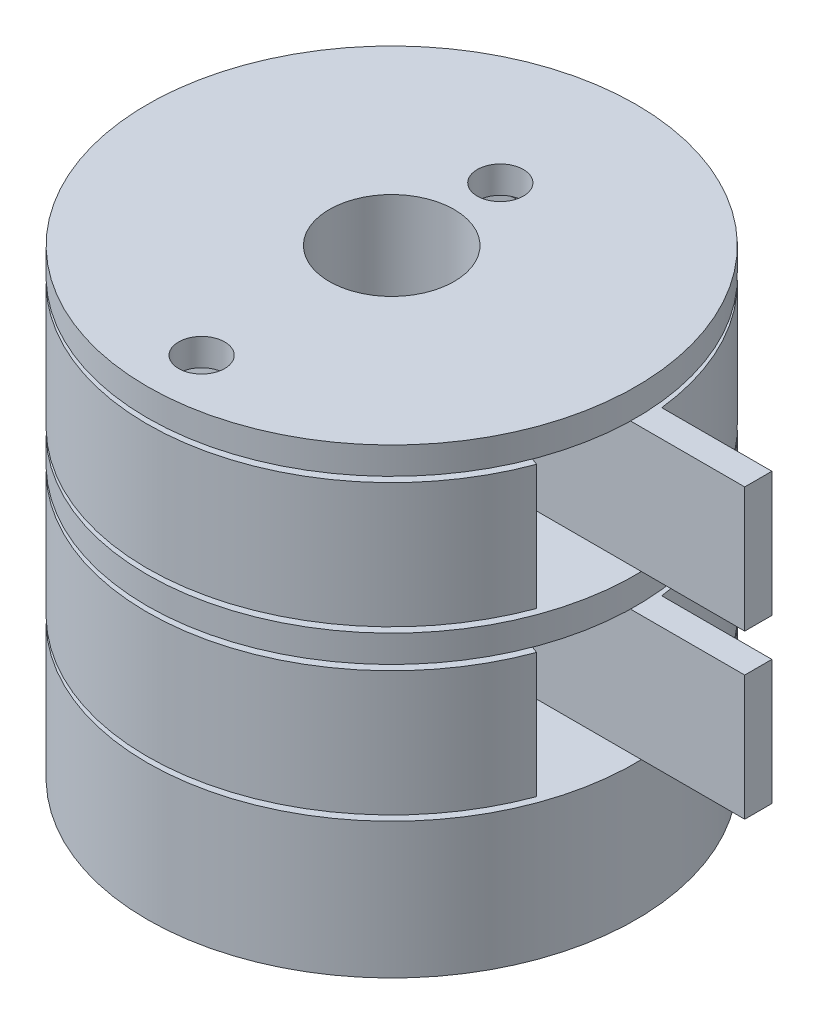
SolidWorks part; units mm, degrees
ref_plane "Plano frontal" through (0, 0, 0) normal (0, 0, 1) x (1, 0, 0)
ref_plane "Plano superior" through (0, 0, 0) normal (0, 1, 0) x (1, 0, 0)
ref_plane "Plano direito" through (0, 0, 0) normal (1, 0, 0) x (0, 0, -1)
sketch "Esboço1" plane through (0, 0, 0) normal (0, 0, 1) x (1, 0, 0)
  line L0 (9, 3.5) -> (3.7, 3.5)
  line L1 (2.3, 9.5) -> (2.3, -7.5)
  line L2 (2.3, -7.5) -> (9, -7.5)
  line L3 (9, -7.5) -> (9, -2.5)
  line L4 (9, -2.5) -> (3.7, -2.5)
  line L5 (3.7, -2.5) -> (3.7, 2.5)
  line L6 (3.7, 2.5) -> (9, 2.5)
  line L7 (9, 2.5) -> (9, 3.5)
  line L8 (0, 0) -> (9.3553, 0) construction
  line L9 (0, 0) -> (0, 2.2181) construction
  line L10 (3.7, 3.5) -> (3.7, 8.5)
  line L11 (3.7, 8.5) -> (9, 8.5)
  line L12 (9, 8.5) -> (9, 9.5)
  line L13 (9, 9.5) -> (2.3, 9.5)
  point P12 (3.7, 0)
  point P15 (1.8, 7.7314)
  dimension "D1" = 4.6
  dimension "D2" = 18
  dimension "D3" = 1.4
  dimension "D4" = 1
  dimension "D5" = 5
  dimension "D6" = 5
revolve "Revolução1" add sketch "Esboço1" angle 360 about L9
sketch "Esboço2" plane through (0, 3.5, 0) normal (0, 1, 0) x (1, 0, 0)
  line L0 (-2.245, 0.5) -> (2.245, 0.5)
  circle A0 centre (0, 0) radius 2.3 construction
  arc A1 (2.245, 0.5) -> (-2.245, 0.5) centre (0, 0) ccw
  arc A2 (-2.245, 0.5) -> (2.245, 0.5) centre (0, 0) ccw construction
  dimension "D1" = 2.8
extrude "Ressalto-extrusão2" [suppressed] add sketch "Esboço2" against normal through all
sketch "Esboço3" plane through (0, 2.5, 0) normal (0, -1, 0) x (1, 0, 0)
  circle A0 centre (0, -4) radius 0.85
  circle A1 centre (0, 7) radius 0.85
  point P4 (0, 0)
  dimension "D3" = 1.7
  dimension "D1" = 7
  dimension "D2" = 4
extrude "Corte-extrusão1" cut sketch "Esboço3" against normal through all both and the other way through all
sketch "Esboço4" plane through (0, 0, 0) normal (1, 0, 0) x (0, 0, -1)
  line L0 (-9, -7.5) -> (9, -7.5) construction
  circle A0 centre (0, -5.1) radius 1.05
  circle A1 centre (0, -5.1) radius 1.6
  circle A2 centre (0, -5.1) radius 2
  dimension "D1" = 2.1
  dimension "D2" = 2.4
  dimension "D3" = 4
  dimension "D4" = 3.2
extrude "Corte-extrusão2" cut sketch "Esboço4" against normal through all contours A0 region at (0, -5.1, 0)
extrude "Corte-extrusão4" cut sketch "Esboço4<3>" against normal through all from offset 7 contours A2 offset against normal yes
sketch "Esboço4<3>" plane through (0, 0, 0) normal (1, 0, 0) x (0, 0, -1) same geometry as "Esboço4"
extrude "Corte-extrusão5" cut sketch "Esboço4<4>" along normal blind 3 from surface contours A1 starting at face at (-7, -5.1, -2)
sketch "Esboço4<4>" plane through (0, 0, 0) normal (1, 0, 0) x (0, 0, -1) same geometry as "Esboço4"
sketch "Esboço6" plane through (0, 2.5, 0) normal (0, -1, 0) x (1, 0, 0)
  line L0 (8.9443, -1) -> (13, -1)
  line L1 (13, -1) -> (13, 0)
  line L2 (13, 0) -> (9, 0)
  line L3 (8.0237, 2.9535) -> (8.446, 3.1089)
  line L4 (9, 0) -> (8.55, 0)
  line L5 (8.55, 0) -> (5.45, 0)
  line L6 (5.45, 0) -> (5, 0)
  line L7 (5.1145, 1.8826) -> (4.6922, 1.7272)
  line L8 (8.4913, -1) -> (5.3575, -1)
  arc A0 (8.446, 3.1089) -> (8.9443, -1) centre (0, 0) ccw
  arc A1 (8.0237, 2.9535) -> (8.4913, -1) centre (0, 0) ccw
  arc A2 (8.55, 0) -> (8.0237, 2.9535) centre (0, 0) ccw construction
  circle A3 centre (0, 0) radius 9 construction
  arc A4 (8.9443, -1) -> (9, 0) centre (0, 0) ccw construction
  arc A5 (9, 0) -> (8.446, 3.1089) centre (0, 0) ccw construction
  arc A6 (5.1145, 1.8826) -> (5.3575, -1) centre (0, 0) ccw
  arc A7 (4.6922, 1.7272) -> (5, 0) centre (0, 0) ccw
  arc A8 (5.45, 0) -> (5.1145, 1.8826) centre (0, 0) ccw construction
  arc A9 (5, 0) -> (4.6922, 1.7272) centre (0, 0) ccw construction
  arc A10 (5.3575, -1) -> (5.45, 0) centre (0, 0) ccw construction
  arc A11 (8.4913, -1) -> (8.55, 0) centre (0, 0) ccw construction
  dimension "D1" = 0.45
  dimension "D5" = 0.45
  dimension "D6" = 5
  dimension "D2" = 1
  dimension "D3" = 4
  dimension "D4" = 3
extrude "Ressalto-extrusão3" add sketch "Esboço6" along normal offset from surface (4.6 mm away) 0.2 from offset 0.2 up to face at (0, -2.5, -0.575)
extrude "Ressalto-extrusão4" add sketch "Esboço6<2>" against normal offset from surface (4.6 mm away) 0.2 from offset 1.2 separate body up to face at (0, 8.5, -0.575) offset against normal yes
sketch "Esboço6<2>" plane through (0, 2.5, 0) normal (0, -1, 0) x (1, 0, 0) same geometry as "Esboço6"
